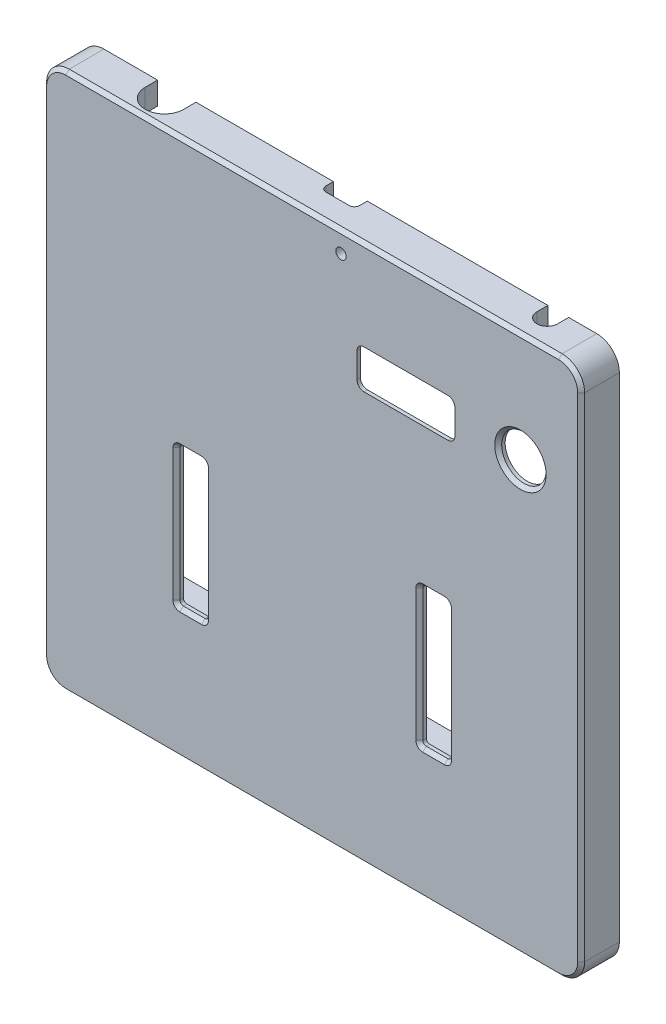
SolidWorks part; units mm, degrees
ref_plane "Front Plane" through (0, 0, 0) normal (0, 0, 1) x (1, 0, 0)
ref_plane "Top Plane" through (0, 0, 0) normal (0, 1, 0) x (1, 0, 0)
ref_plane "Right Plane" through (0, 0, 0) normal (1, 0, 0) x (0, 0, -1)
sketch "Sketch2" plane through (0, 0, 42.3665) normal (0, 0, 1) x (1, 0, 0)
  line L31 (-77.9262, 247.7653) -> (37.5488, 247.7653) construction
  line L32 (44.0488, 241.2653) -> (44.0488, 99.2653) construction
  line L35 (37.5488, 92.7653) -> (-104.4512, 92.7653) construction
  line L36 (-110.9512, 99.2653) -> (-110.9512, 241.2653) construction
  line L37 (-104.4512, 247.7653) -> (37.5488, 247.7653)
  line L38 (44.0488, 241.2653) -> (44.0488, 99.2653)
  line L39 (37.5488, 92.7653) -> (-104.4512, 92.7653)
  line L40 (-110.9512, 99.2653) -> (-110.9512, 241.2653)
  line L41 (-104.4512, 236.2653) -> (-104.4512, 176.7653)
  line L43 (37.5488, 127.586) -> (37.5488, 171.7653)
  line L44 (32.5488, 241.2653) -> (-22.2512, 241.2653)
  line L45 (-28.0512, 241.2653) -> (-28.0512, 239.2653)
  line L46 (-28.0512, 239.2653) -> (-22.2512, 239.2653)
  line L47 (-22.2512, 239.2653) -> (-22.2512, 241.2653)
  line L50 (-99.4512, 241.2653) -> (-104.4512, 236.2653)
  line L51 (37.5488, 236.2653) -> (32.5488, 241.2653)
  line L52 (-35.9512, 171.7653) -> (-35.9512, 127.586)
  line L53 (-104.4512, 176.7653) -> (37.5488, 176.7653)
  line L55 (-104.4512, 171.7653) -> (-35.9512, 171.7653)
  line L57 (-35.9512, 127.586) -> (-104.4512, 127.586)
  line L58 (-28.0512, 241.2653) -> (-99.4512, 241.2653)
  line L59 (-35.9512, 149.6756) -> (-33.4512, 149.6756) construction
  line L62 (-30.9512, 171.7653) -> (-30.9512, 127.586)
  line L63 (-30.9512, 127.586) -> (37.5488, 127.586)
  line L64 (-33.4512, 149.6756) -> (-30.9512, 149.6756) construction
  line L65 (-30.9512, 171.7653) -> (37.5488, 171.7653)
  line L66 (-104.4512, 171.7653) -> (-104.4512, 127.586)
  line L67 (37.5488, 176.7653) -> (37.5488, 236.2653)
  line L68 (-25.5512, 242.3153) -> (-25.5512, 241.4153) construction
  line L69 (-24.7512, 242.3153) -> (-24.7512, 241.4153) construction
  line L70 (-33.4512, 176.7653) -> (-33.4512, 178.2653) construction
  line L71 (-100.4512, 178.2653) -> (33.5488, 178.2653) construction
  line L72 (-75.1287, 171.7653) -> (-75.1287, 170.2653) construction
  line L73 (-45.4512, 170.2653) -> (-92.4512, 170.2653) construction
  arc A1 (44.0488, 241.2653) -> (37.5488, 247.7653) centre (37.5488, 241.2653) ccw construction
  arc A5 (37.5488, 92.7653) -> (44.0488, 99.2653) centre (37.5488, 99.2653) ccw construction
  arc A6 (-110.9512, 99.2653) -> (-104.4512, 92.7653) centre (-104.4512, 99.2653) ccw construction
  arc A7 (-104.4512, 247.7653) -> (-110.9512, 241.2653) centre (-104.4512, 241.2653) ccw construction
  arc A8 (44.0488, 241.2653) -> (37.5488, 247.7653) centre (37.5488, 241.2653) ccw
  arc A9 (37.5488, 92.7653) -> (44.0488, 99.2653) centre (37.5488, 99.2653) ccw
  arc A10 (-110.9512, 99.2653) -> (-104.4512, 92.7653) centre (-104.4512, 99.2653) ccw
  arc A11 (-104.4512, 247.7653) -> (-110.9512, 241.2653) centre (-104.4512, 241.2653) ccw
  line M3 (-77.9262, 245.7653) -> (37.5488, 245.7653)
  arc M4 (37.5488, 245.7653) -> (42.0488, 241.2653) centre (37.5488, 241.2653) cw
  line M5 (42.0488, 241.2653) -> (42.0488, 99.2653)
  arc M6 (42.0488, 99.2653) -> (37.5488, 94.7653) centre (37.5488, 99.2653) cw
  line M7 (37.5488, 94.7653) -> (-104.4512, 94.7653)
  arc M8 (-104.4512, 94.7653) -> (-108.9512, 99.2653) centre (-104.4512, 99.2653) cw
  line M9 (-108.9512, 99.2653) -> (-108.9512, 241.2653)
  arc M10 (-108.9512, 241.2653) -> (-104.4512, 245.7653) centre (-104.4512, 241.2653) cw
  line M11 (-104.4512, 245.7653) -> (-88.9762, 245.7653)
  line M13 (-88.9762, 247.7653) -> (-104.4512, 247.7653)
  arc M14 (-104.4512, 247.7653) -> (-110.9512, 241.2653) centre (-104.4512, 241.2653) ccw
  line M15 (-110.9512, 241.2653) -> (-110.9512, 99.2653)
  arc M16 (-110.9512, 99.2653) -> (-104.4512, 92.7653) centre (-104.4512, 99.2653) ccw
  line M17 (-104.4512, 92.7653) -> (37.5488, 92.7653)
  arc M18 (37.5488, 92.7653) -> (44.0488, 99.2653) centre (37.5488, 99.2653) ccw
  line M19 (44.0488, 99.2653) -> (44.0488, 241.2653)
  arc M20 (44.0488, 241.2653) -> (37.5488, 247.7653) centre (37.5488, 241.2653) ccw
  line M21 (37.5488, 247.7653) -> (-77.9262, 247.7653)
  dimension "D2" = 2.5
  dimension "D3" = 2
  dimension "D4" = 5
  dimension "D5" = 5
  dimension "D7" = 2.5
extrude "Boss-Extrude1" add sketch "Sketch2" along normal blind 9 contours L37 L67 L53 L41 L50 L44 L51 L66 L55 L52 L57 L62 L65 L43 L63 M11 M10 M9 M8 M7 M6 M5 M4 M3 | M21 M3 M4 M5 M6 M7 M8 M9 M10 M11 M13 M14 M15 M16 M17 M18 M19 M20 region at (-33.4403, 144.4255, 42.3665)
fillet "Fillet1" radius 4 14 edges at (37.5488, 171.7653, 46.8665) (37.5488, 127.586, 46.8665) (-30.9512, 127.586, 46.8665) (-104.4512, 127.586, 46.8665) (-35.9512, 127.586, 46.8665) (-104.4512, 171.7653, 46.8665) (-35.9512, 171.7653, 46.8665) (-30.9512, 171.7653, 46.8665) (32.5488, 241.2653, 46.8665) (37.5488, 236.2653, 46.8665) (37.5488, 176.7653, 46.8665) (-104.4512, 176.7653, 46.8665) (-104.4512, 236.2653, 46.8665) (-99.4512, 241.2653, 46.8665)
sketch "Sketch4" plane through (0, 0, 51.3665) normal (0, 0, 1) x (1, 0, 0)
  line L8 (-104.4512, 92.7653) -> (37.5488, 92.7653) construction
  line L9 (44.0488, 99.2653) -> (44.0488, 241.2653) construction
  line L10 (-104.4512, 247.7653) -> (37.5488, 247.7653) construction
  line L11 (-110.9512, 241.2653) -> (-110.9512, 99.2653) construction
  line L12 (-104.4512, 92.7653) -> (37.5488, 92.7653)
  line L13 (44.0488, 99.2653) -> (44.0488, 241.2653)
  line L14 (-104.4512, 247.7653) -> (37.5488, 247.7653)
  line L15 (-110.9512, 241.2653) -> (-110.9512, 99.2653)
  arc A8 (-110.9512, 99.2653) -> (-104.4512, 92.7653) centre (-104.4512, 99.2653) ccw construction
  arc A9 (37.5488, 92.7653) -> (44.0488, 99.2653) centre (37.5488, 99.2653) ccw construction
  arc A10 (44.0488, 241.2653) -> (37.5488, 247.7653) centre (37.5488, 241.2653) ccw construction
  arc A11 (-104.4512, 247.7653) -> (-110.9512, 241.2653) centre (-104.4512, 241.2653) ccw construction
  arc A12 (-110.9512, 99.2653) -> (-104.4512, 92.7653) centre (-104.4512, 99.2653) ccw
  arc A13 (37.5488, 92.7653) -> (44.0488, 99.2653) centre (37.5488, 99.2653) ccw
  arc A14 (44.0488, 241.2653) -> (37.5488, 247.7653) centre (37.5488, 241.2653) ccw
  arc A15 (-104.4512, 247.7653) -> (-110.9512, 241.2653) centre (-104.4512, 241.2653) ccw
extrude "Boss-Extrude2" add sketch "Sketch4" along normal blind 2
sketch "Sketch5" plane through (0, 0, 53.3665) normal (0, 0, 1) x (1, 0, 0)
  circle A0 centre (26.5488, 216.3153) radius 6.4
  arc A3 (20.6592, 215.9653) -> (20.6592, 216.6653) centre (26.5488, 216.3153) ccw construction
  dimension "D1" = 0.5
extrude "Cut-Extrude2" cut sketch "Sketch5" against normal up to next
sketch "Sketch9" plane through (0, 247.7653, 0) normal (0, 1, 0) x (1, 0, 0)
  line L0 (-28.9512, -40.6665) -> (-37.9512, -40.6665) construction
  line L5 (-77.9262, -42.3665) -> (37.5488, -42.3665) construction
  line L7 (23.4604, -45.5474) -> (23.4604, -42.3665)
  line L8 (23.4604, -42.3665) -> (29.4604, -42.3665)
  line L9 (29.4604, -45.5474) -> (29.4604, -42.3665)
  line L11 (-104.4512, -42.3665) -> (37.5488, -42.3665) construction
  line L12 (-28.5762, -42.3665) -> (-38.3262, -42.3665)
  line L13 (-38.3262, -42.3665) -> (-38.3262, -44.5665)
  line L14 (-36.8262, -46.0665) -> (-30.0762, -46.0665)
  line L16 (-28.5762, -42.3665) -> (-28.5762, -44.5665)
  line L17 (-88.9762, -42.3665) -> (-77.9262, -42.3665)
  line L20 (-88.9762, -45.9323) -> (-88.9762, -42.3665)
  line L22 (-77.9262, -45.9323) -> (-77.9262, -42.3665)
  arc A1 (-38.3262, -44.5665) -> (-36.8262, -46.0665) centre (-36.8262, -44.5665) ccw
  arc A3 (23.4604, -45.5474) -> (29.4604, -45.5474) centre (26.4604, -45.5474) ccw
  circle A4 centre (26.4604, -45.5474) radius 2.5 construction
  arc A5 (-28.5762, -44.5665) -> (-30.0762, -46.0665) centre (-30.0762, -44.5665) cw
  arc A6 (-88.9762, -45.9323) -> (-77.9262, -45.9323) centre (-83.4512, -45.9323) ccw
  arc A7 (-79.2309, -42.3665) -> (-87.6715, -42.3665) centre (-83.4512, -45.9323) ccw construction
  point P2 (-88.8114, -42.3665)
  point P26 (-33.4512, -40.6665)
  point P29 (-38.3262, -46.0665)
  point P34 (-33.4512, -42.3665)
  point P35 (-75.9924, -45.9323)
  point P36 (-77.9262, -45.9323)
  dimension "D1" = 0.5
  dimension "D4" = 1.5
  dimension "D5" = 1.5
  dimension "D2" = 3.7
  dimension "D3" = 9.75
extrude "Cut-Extrude6" cut sketch "Sketch9" against normal blind 13
sketch "Sketch7" plane through (0, 0, 53.3665) normal (0, 0, 1) x (1, 0, 0)
  line L0 (-69.9117, 132.263) -> (-65.4667, 132.263) construction
  line L17 (-65.4667, 132.263) -> (-65.4667, 168.2675) construction
  line L18 (-71.4357, 166.7435) -> (-71.4357, 133.787) construction
  line L19 (-65.4667, 168.2675) -> (-69.9117, 168.2675) construction
  line L25 (-67.6892, 170.2653) -> (-67.6892, 168.2675) construction
  line L26 (-64.3262, 130.2653) -> (-72.5762, 130.2653)
  line L27 (-64.3262, 130.2653) -> (-64.3262, 170.2653)
  line L28 (-64.3262, 170.2653) -> (-72.5762, 170.2653)
  line L29 (-72.5762, 130.2653) -> (-72.5762, 170.2653)
  line L31 (-72.5762, 165.4811) -> (-71.4357, 165.4811) construction
  line L33 (-64.3262, 166.2075) -> (-65.4667, 166.2075) construction
  line L35 (-66.833, 130.2653) -> (-66.833, 132.263) construction
  point P0 (-67.6892, 168.2675)
  dimension "D3" = 8.25
  dimension "D4" = 40
extrude "Cut-Extrude4" cut sketch "Sketch7" against normal up to next
fillet "Fillet4" radius 1 4 edges at (-72.5762, 130.2653, 52.3665) (-64.3262, 130.2653, 52.3665) (-64.3262, 170.2653, 52.3665) (-72.5762, 170.2653, 52.3665)
pattern_linear "LPattern1" count 2 spacing 70 along (1, 0, 0) of "Fillet4", "Cut-Extrude4"
sketch "Sketch8" plane through (0, 0, 53.3665) normal (0, 0, 1) x (1, 0, 0)
  line L1 (7.0488, 211.3153) -> (-19.9512, 211.3153) construction
  line L2 (7.0488, 211.3153) -> (7.0488, 221.3153) construction
  line L3 (7.0488, 221.3153) -> (-19.9512, 221.3153) construction
  line L4 (-19.9512, 211.3153) -> (-19.9512, 221.3153) construction
  line L5 (7.6488, 212.7153) -> (7.6488, 219.9153)
  line L6 (44.0488, 99.2653) -> (44.0488, 241.2653) construction
  line L7 (-19.9512, 208.3153) -> (9.0488, 208.3153)
  line L8 (-21.9512, 210.3153) -> (-21.9512, 221.3153)
  line L9 (-19.9512, 223.3153) -> (9.0488, 223.3153)
  line L10 (11.0488, 210.3153) -> (11.0488, 221.3153)
  line L11 (5.6488, 221.9153) -> (-18.5512, 221.9153)
  line L12 (-20.5512, 212.7153) -> (-20.5512, 219.9153)
  line L13 (5.6488, 210.7153) -> (-18.5512, 210.7153)
  line L14 (7.6488, 210.7153) -> (7.6488, 221.9153) construction
  line L15 (7.6488, 210.7153) -> (-20.5512, 210.7153) construction
  line L16 (-20.5512, 210.7153) -> (-20.5512, 221.9153) construction
  line L17 (7.6488, 221.9153) -> (-20.5512, 221.9153) construction
  line L18 (-104.4512, 90.7653) -> (37.5488, 90.7653)
  line L19 (46.0488, 99.2653) -> (46.0488, 241.2653)
  line L20 (37.5488, 249.7653) -> (-104.4512, 249.7653)
  line L21 (-112.9512, 241.2653) -> (-112.9512, 99.2653)
  line L22 (-104.4512, 90.7653) -> (37.5488, 90.7653)
  line L23 (46.0488, 99.2653) -> (46.0488, 241.2653)
  line L24 (37.5488, 249.7653) -> (-104.4512, 249.7653)
  line L25 (-112.9512, 241.2653) -> (-112.9512, 99.2653)
  line L26 (20.1488, 216.3153) -> (32.9488, 216.3153) construction
  line L27 (-20.5512, 216.3153) -> (7.6488, 216.3153) construction
  arc A0 (7.6488, 212.7153) -> (5.6488, 210.7153) centre (5.6488, 212.7153) cw
  arc A1 (-20.5512, 212.7153) -> (-18.5512, 210.7153) centre (-18.5512, 212.7153) ccw
  arc A2 (-18.5512, 221.9153) -> (-20.5512, 219.9153) centre (-18.5512, 219.9153) ccw
  arc A3 (7.6488, 219.9153) -> (5.6488, 221.9153) centre (5.6488, 219.9153) ccw
  circle A4 centre (26.5488, 216.3153) radius 6.4 construction
  arc A5 (9.0488, 223.3153) -> (11.0488, 221.3153) centre (9.0488, 221.3153) cw
  arc A6 (9.0488, 208.3153) -> (11.0488, 210.3153) centre (9.0488, 210.3153) ccw
  arc A7 (-19.9512, 208.3153) -> (-21.9512, 210.3153) centre (-19.9512, 210.3153) cw
  arc A8 (-112.9512, 99.2653) -> (-104.4512, 90.7653) centre (-104.4512, 99.2653) ccw
  arc A9 (37.5488, 90.7653) -> (46.0488, 99.2653) centre (37.5488, 99.2653) ccw
  arc A10 (46.0488, 241.2653) -> (37.5488, 249.7653) centre (37.5488, 241.2653) ccw
  arc A11 (-104.4512, 249.7653) -> (-112.9512, 241.2653) centre (-104.4512, 241.2653) ccw
  arc A12 (-112.9512, 99.2653) -> (-104.4512, 90.7653) centre (-104.4512, 99.2653) ccw
  arc A13 (37.5488, 90.7653) -> (46.0488, 99.2653) centre (37.5488, 99.2653) ccw
  arc A14 (46.0488, 241.2653) -> (37.5488, 249.7653) centre (37.5488, 241.2653) ccw
  arc A15 (-104.4512, 249.7653) -> (-112.9512, 241.2653) centre (-104.4512, 241.2653) ccw
  arc A16 (-21.9512, 221.3153) -> (-19.9512, 223.3153) centre (-19.9512, 221.3153) cw
  point P42 (11.0488, 208.3153)
  point P51 (-21.9512, 208.3153)
  point P54 (-21.9512, 223.3153)
  dimension "D11" = 2
  dimension "D3" = 2
  dimension "D1" = 27
  dimension "D2" = 10
  dimension "D4" = 37
  dimension "D5" = 33
  dimension "D6" = 15
  dimension "D7" = 2
  dimension "D8" = 2
  dimension "D9" = 2
  dimension "D10" = 0.6
extrude "Cut-Extrude5" cut sketch "Sketch8" against normal up to next contours L5 A3 L11 A2 L12 A1 L13 A0 region at (-6.4512, 216.3153, 53.3665)
extrude "Cut-Extrude13" cut sketch "Sketch8<3>" along normal offset from surface (1 mm away) 1 from surface contours A16 L8 A7 L7 A6 L10 A5 L9 A3 L5 A0 L13 A1 L12 A2 L11 region at (-21.1091, 209.1574, 53.3665) up to face at (-6.4512, 216.3153, 53.3665) starting at face at (-6.4512, 216.3153, 51.3665)
sketch "Sketch8<3>" plane through (0, 0, 53.3665) normal (0, 0, 1) x (1, 0, 0) same geometry as "Sketch8"
chamfer "Chamfer1" distance 1 angle 45 25 edges at (32.9488, 216.3153, 53.3665) (-110.9512, 170.2653, 53.3665) (-109.0474, 245.8614, 53.3665) (-33.4512, 247.7653, 53.3665) (42.145, 245.8614, 53.3665) (44.0488, 170.2653, 53.3665) (42.145, 94.6691, 53.3665) (-33.4512, 92.7653, 53.3665) (-109.0474, 94.6691, 53.3665) (-64.6191, 169.9724, 53.3665) (-68.4512, 170.2653, 53.3665) (-72.2833, 169.9724, 53.3665) (-72.5762, 150.2653, 53.3665) (-72.2833, 130.5581, 53.3665) (-68.4512, 130.2653, 53.3665) (-64.6191, 130.5581, 53.3665) (-64.3262, 150.2653, 53.3665) (5.3809, 169.9724, 53.3665) (1.5488, 170.2653, 53.3665) (-2.2833, 169.9724, 53.3665) (-2.5762, 150.2653, 53.3665) (-2.2833, 130.5581, 53.3665) (1.5488, 130.2653, 53.3665) (5.3809, 130.5581, 53.3665) (5.6738, 150.2653, 53.3665)
fillet "Fillet5" radius 2 2 edges at (-28.0512, 241.2653, 46.8665) (-22.2512, 241.2653, 46.8665)
fillet "Fillet6" radius 2 2 edges at (-22.2512, 239.2653, 46.8665) (-28.0512, 239.2653, 46.8665)
sketch "Sketch10" plane through (0, 0, 53.3665) normal (0, 0, 1) x (1, 0, 0)
  line L0 (-30.0512, 241.2653) -> (-25.1512, 241.8653) construction
  line L1 (-25.1512, 241.8653) -> (-20.2512, 241.2653) construction
  line L2 (37.5488, 246.7653) -> (-104.4512, 246.7653) construction
  line L3 (-30.0512, 241.2653) -> (-82.4537, 241.2653) construction
  circle A0 centre (-25.1512, 241.8653) radius 1.5
  point P2 (-25.1637, 243.7737)
  point P10 (-30.5781, 241.2653)
  point P13 (-30.1691, 241.2653)
  point P15 (-30.0512, 241.2653)
  dimension "D1" = 3
  dimension "D2" = 4.9
extrude "Cut-Extrude11" cut sketch "Sketch10" along direction (0, 0, -1) on the side against the normal through all
hole_wizard "M3x0.5 Tapped Hole1" positions "Sketch11" profile "Sketch12" tap size "M3x0.5" standard "ANSI Metric"
sketch "Sketch11" plane through (0, 0, 42.3665) normal (0, 0, -1) x (-1, 0, 0)
  point P0 (-37.5488, 241.2653)
  point P3 (-37.5488, 99.2653)
  point P6 (104.4512, 99.2653)
  point P9 (104.4512, 241.2653)
sketch "Sketch12" plane through (37.5488, 241.2653, 42.3665) normal (1, 0, 0) x (0, 1, 0)
  line L0 (0, 0) -> (0, 7)
  line L1 (0, 7) -> (1.25, 6.2489)
  line L2 (1.25, 6.2489) -> (1.25, 0)
  line L5 (1.25, 0) -> (0, 0)
  line L10 (0, 7) -> (-1.25, 6.2489) construction
  line L11 (0, -6.35) -> (0, 107.95) construction
  dimension "Tap Drill Dia." = 2.5
  dimension "Tap Drill Depth" = 7
  dimension "Drill Angle" = 118
cosmetic thread "Hole Thread1" parameters "D1"=7, "D2"=3
cosmetic thread "Hole Thread2" parameters "D1"=7, "D2"=3
cosmetic thread "Hole Thread3" parameters "D1"=7, "D2"=3
cosmetic thread "Hole Thread4" parameters "D1"=7, "D2"=3
sketch "Sketch13" plane through (0, 0, 42.3665) normal (0, 0, -1) x (-1, 0, 0)
  line L1 (30.0762, 244.5153) -> (20.2512, 244.5153)
  line L2 (30.0762, 244.5153) -> (30.0762, 237.2344)
  line L3 (30.0762, 237.2344) -> (20.2512, 237.2344)
  line L4 (20.2512, 244.5153) -> (20.2512, 237.2344)
  line L6 (30.0762, 241.2653) -> (30.0762, 247.7653) construction
  point P4 (30.0762, 244.5153)
  point P6 (28.5762, 244.1906)
  point P9 (28.5762, 237.2344)
  point P10 (20.7268, 244.1906)
extrude "Cut-Extrude12" cut sketch "Sketch13" against normal up to surface (3.7 mm away) contours L3 L4 L1 L2 up to face at (-33.4512, 244.5153, 46.0665)
fillet "Fillet7" radius 2 1 edges at (-20.2512, 244.5153, 44.2165)
